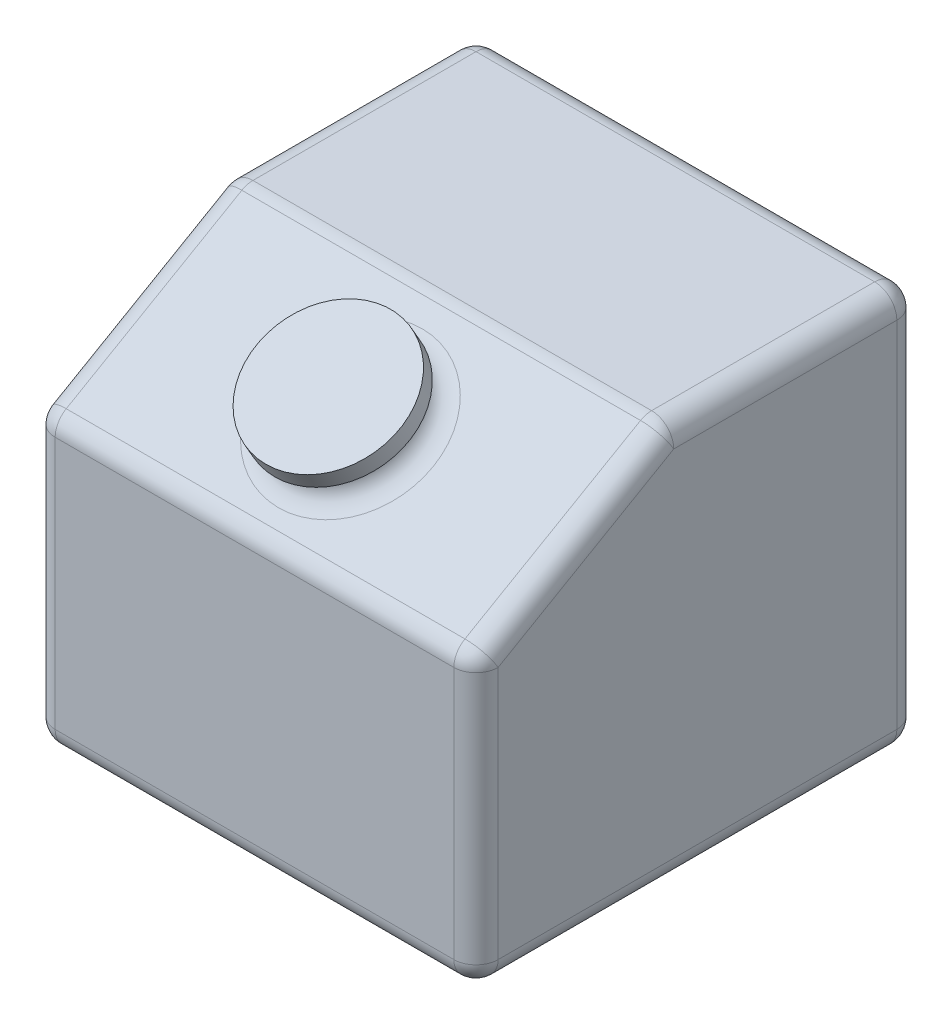
SolidWorks part; units mm, degrees
ref_plane "정면" through (0, 0, 0) normal (0, 0, 1) x (1, 0, 0)
ref_plane "윗면" through (0, 0, 0) normal (0, 1, 0) x (1, 0, 0)
ref_plane "우측면" through (0, 0, 0) normal (1, 0, 0) x (0, 0, -1)
sketch "스케치1" plane through (0, 0, 0) normal (0, 1, 0) x (1, 0, 0)
  line L1 (0, 0) -> (200, 0)
  line L2 (0, 0) -> (0, 200)
  line L3 (0, 200) -> (200, 200)
  line L4 (200, 0) -> (200, 200)
  dimension "D1" = 200
  dimension "D2" = 200
extrude "보스-돌출1" add sketch "스케치1" along normal blind 180
chamfer "모따기1" distance 50 angle 60 1 edges at (100, 180, 0) first distance on face at (100, 90, 0)
sketch "스케치2" plane through (0, 97.5, 56.2917) normal (0, 0.866, 0.5) x (1, 0, 0)
  line L0 (100, 325.5953) -> (100, -95.5953) construction
  line L1 (-60.6396, 115) -> (260.6396, 115) construction
  line L2 (200, 165) -> (200, 65) construction
  line L3 (200, 65) -> (0, 65) construction
  circle A0 centre (100, 115) radius 32.5
  circle A1 centre (100, 115) radius 27.5
  point P4 (100, 115)
  point P7 (200, 115)
  point P9 (100, 115)
  point P13 (100, 65)
  dimension "D1" = 65
  dimension "D2" = 55
extrude "보스-돌출2" add sketch "스케치2" along normal blind 20 contours A1 region at (100, 155, -43.3013)
extrude "보스-돌출3" add sketch "스케치2<3>" against normal blind 8 from offset 20
sketch "스케치2<3>" plane through (0, 97.5, 56.2917) normal (0, 0.866, 0.5) x (1, 0, 0) same geometry as "스케치2"
fillet "필렛1" radius 10 16 edges at (100, 141.25, -19.4856) (100, 180, -86.6025) (0, 180, -143.3013) (0, 155, -43.3013) (100, 180, -200) (0, 90, -200) (200, 90, -200) (200, 155, -43.3013) (200, 180, -143.3013) (0, 65, 0) (100, 130, 0) (200, 65, 0) (100, 0, 0) (200, 0, -100) (100, 0, -200) (0, 0, -100)
sketch "스케치3" plane through (200, 0, 0) normal (1, 0, 0) x (0, 0, -1)
  line L10 (187, 13) -> (187, 167)
  line L11 (187, 167) -> (90.0859, 167)
  line L12 (90.0859, 167) -> (13, 122.4944)
  line L13 (13, 122.4944) -> (13, 13)
  line L14 (13, 13) -> (187, 13)
  line L15 (187, 13) -> (187, 167)
  line L16 (187, 167) -> (90.0859, 167)
  line L17 (90.0859, 167) -> (13, 122.4944)
  line L18 (13, 122.4944) -> (13, 13)
  line L19 (13, 13) -> (187, 13)
  dimension "D1" = 3
extrude "컷-돌출1" cut sketch "스케치3" against normal blind 180 from offset 10 offset against normal yes
